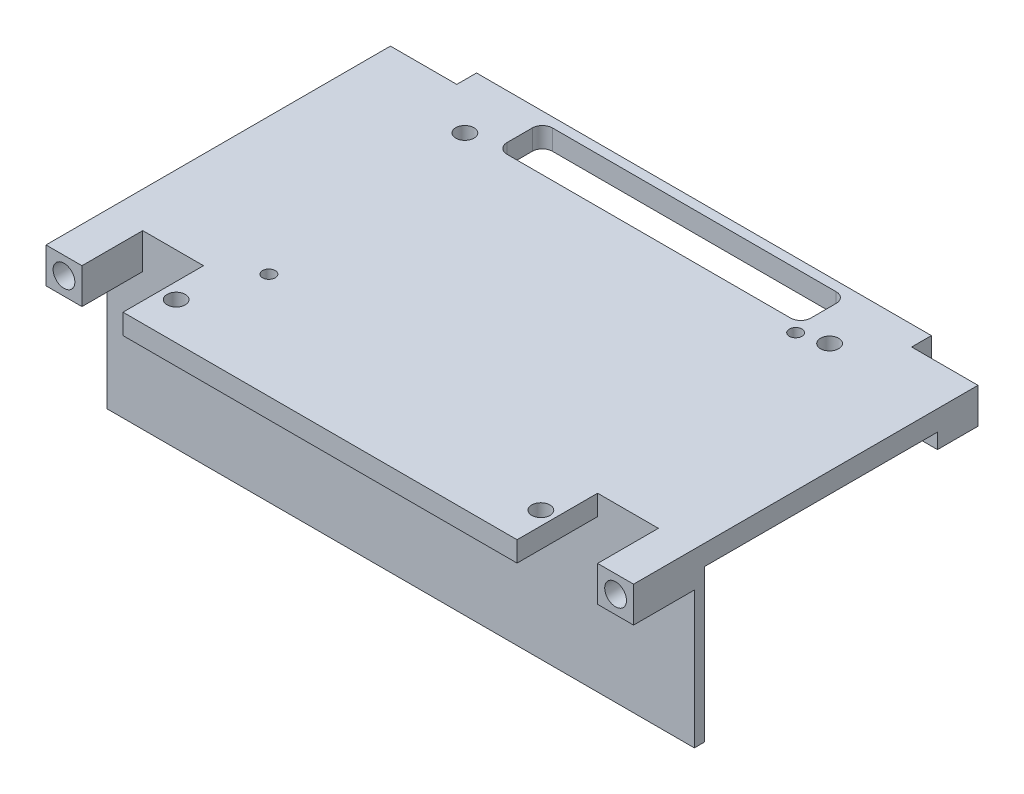
SolidWorks part; units mm, degrees
ref_plane "Front Plane" through (0, 0, 0) normal (0, 0, 1) x (1, 0, 0)
ref_plane "Top Plane" through (0, 0, 0) normal (0, 1, 0) x (1, 0, 0)
ref_plane "Right Plane" through (0, 0, 0) normal (1, 0, 0) x (0, 0, -1)
sketch "Sketch1" plane through (0, 0, 0) normal (0, 1, 0) x (1, 0, 0)
  line L0 (-58, 0) -> (58, 0) construction
  line L1 (-58, -34) -> (-50.9, -34)
  line L2 (-58, -34) -> (-58, 34)
  line L3 (-58, 34) -> (-50.9, 34)
  line L4 (58, -34) -> (58, 34)
  line L5 (-58, -34) -> (58, 34) construction
  line L6 (-58, 34) -> (58, -34) construction
  line L8 (-50.9, 34) -> (-50.9, 41)
  line L9 (-50.9, 41) -> (50.9, 41)
  line L10 (50.9, 34) -> (50.9, 41)
  line L11 (50.9, 34) -> (58, 34)
  line L12 (50.9, -34) -> (50.9, -41)
  line L13 (-50.9, -41) -> (50.9, -41)
  line L14 (-50.9, -34) -> (-50.9, -41)
  line L15 (50.9, -34) -> (58, -34)
  point P0 (0, 0)
  point P10 (0, 41)
  dimension "D1" = 116
  dimension "D2" = 68
  dimension "D3" = 7.1
  dimension "D4" = 7
extrude "Boss-Extrude1" add sketch "Sketch1" along normal blind 4
sketch "Sketch3" plane through (0, 0, 0) normal (0, -1, 0) x (1, 0, 0)
  line L0 (-58, -34) -> (-58, 34) construction
  line L1 (-50.9, -34) -> (-58, -34)
  line L2 (-50.9, -34) -> (-50.9, -26)
  line L3 (-50.9, -26) -> (-58, -26)
  line L4 (-58, -34) -> (-58, -26)
  dimension "D1" = 8
extrude "Boss-Extrude3" add sketch "Sketch3" along normal blind 3
sketch "Sketch4" plane through (0, 0, -34) normal (0, 0, -1) x (-1, 0, 0)
  line L0 (58, -3) -> (50.9, 4) construction
  circle A0 centre (54.45, 0.5) radius 2.15
  dimension "D1" = 4.3
extrude "Cut-Extrude1" cut sketch "Sketch4" against normal blind 7
mirror "Mirror1" about plane through (0, 0, 0) normal (1, 0, 0) of "Cut-Extrude1", "Boss-Extrude3"
mirror "Mirror2" about plane through (0, 0, 0) normal (0, 0, 1) of "Cut-Extrude1", "Boss-Extrude3", "Mirror1"
sketch "Sketch5" plane through (0, 4, 0) normal (0, 1, 0) x (1, 0, 0)
  line L0 (50.9, 41) -> (-50.9, 41) construction
  line L1 (-30, 36) -> (30, 36)
  line L2 (-30, 36) -> (-30, 27)
  line L3 (-30, 27) -> (30, 27)
  line L4 (30, 36) -> (30, 27)
  point P4 (0, 27)
  dimension "D1" = 5
  dimension "D2" = 9
  dimension "D3" = 60
extrude "Cut-Extrude2" cut sketch "Sketch5" against normal through all
sketch "Sketch6" plane through (0, 4, 0) normal (0, 1, 0) x (1, 0, 0)
  line L1 (-38.5, -28) -> (38.5, -28) construction
  line L2 (-38.5, -28) -> (-38.5, 24) construction
  line L3 (-38.5, 24) -> (38.5, 24) construction
  line L4 (38.5, -28) -> (38.5, 24) construction
  line L5 (-38.5, -28) -> (38.5, 24) construction
  line L6 (-38.5, 24) -> (38.5, -28) construction
  circle A0 centre (-38.5, 24) radius 1.25
  circle A1 centre (38.5, 24) radius 1.25
  circle A2 centre (38.5, -28) radius 1.25
  circle A3 centre (-38.5, -28) radius 1.25
  point P0 (0, -2)
  point P9 (0, -2)
  dimension "D4" = 2.5
  dimension "D1" = 77
  dimension "D2" = 52
  dimension "D3" = 2
fillet "Fillet1" radius 2 4 edges at (-30, 2, -36) (-30, 2, -27) (30, 2, -36) (30, 2, -27)
sketch "Sketch7" plane through (0, 4, 0) normal (0, 1, 0) x (1, 0, 0)
  line L0 (50.9, 34) -> (50.9, 41) construction
  line L1 (-50.9, 41) -> (50.9, 41)
  line L2 (-50.9, 41) -> (-50.9, 40)
  line L3 (-50.9, 40) -> (50.9, 40)
  line L4 (50.9, 41) -> (50.9, 40)
  line L5 (-50.9, -34) -> (-50.9, -41) construction
  line L6 (50.9, -41) -> (-50.9, -41)
  line L7 (50.9, -41) -> (50.9, -40)
  line L8 (50.9, -40) -> (-50.9, -40)
  line L9 (-50.9, -41) -> (-50.9, -40)
  dimension "D1" = 1
  dimension "D2" = 1
extrude "Cut-Extrude3" cut sketch "Sketch7" against normal through all
sketch "Sketch8" plane through (0, 0, 0) normal (0, -1, 0) x (1, 0, 0)
  line L0 (58, 26) -> (58, -26) construction
  line L1 (58, 22) -> (-58, 22)
  line L2 (58, 22) -> (58, 20)
  line L3 (58, 20) -> (-58, 20)
  line L4 (-58, 22) -> (-58, 20)
  line L5 (-58, -26) -> (-58, 26) construction
  line L7 (50.9, 40) -> (-50.9, 40) construction
  dimension "D1" = 20
  dimension "D2" = 2
extrude "Boss-Extrude4" add sketch "Sketch8" along normal blind 30
sketch "Sketch9" plane through (0, 4, 0) normal (0, 1, 0) x (1, 0, 0)
  line L0 (58, -22) -> (-58, -22) construction
  line L1 (-50.9, -40) -> (-38.9, -40)
  line L2 (-50.9, -40) -> (-50.9, -22)
  line L3 (-50.9, -22) -> (-38.9, -22)
  line L4 (-38.9, -40) -> (-38.9, -22)
  dimension "D1" = 12
extrude "Cut-Extrude4" cut sketch "Sketch9" against normal blind 10
sketch "Sketch10" plane through (0, -3, 0) normal (0, -1, 0) x (1, 0, 0)
  line L1 (-58, 26) -> (-50.9, 26)
  line L2 (-58, 26) -> (-58, 22)
  line L3 (-58, 22) -> (-50.9, 22)
  line L4 (-50.9, 26) -> (-50.9, 22)
  line L5 (50.9, 26) -> (58, 26)
  line L6 (50.9, 26) -> (50.9, 22)
  line L7 (50.9, 22) -> (58, 22)
  line L8 (58, 26) -> (58, 22)
extrude "Boss-Extrude5" add sketch "Sketch10" against normal up to surface (3 mm away) up to face at (27.2714, 0, 30)
ref_plane "Plane2" through (-51, 0, 0) normal (-1, 0, 0) x (0, 0, 1)
sketch "Sketch12" plane through (-51, 0, 0) normal (-1, 0, 0) x (0, 0, 1)
  line L0 (22, -5.8) -> (22, -16.2)
  line L1 (22, -30) -> (22, -3) construction
  line L2 (22, -16.2) -> (24.7, -13.5)
  line L3 (24.7, -13.5) -> (24.7, -8.5)
  line L4 (24.7, -8.5) -> (22, -5.8)
  line L5 (24.7, -11) -> (22, -11) construction
  line L6 (22, -3) -> (34, -3) construction
  line L7 (24.1, -9) -> (22.6, -9)
  line L8 (24.1, -9) -> (24.1, -13)
  line L9 (24.1, -13) -> (22.6, -13)
  line L10 (22.6, -9) -> (22.6, -13)
  line L11 (22, -20.8) -> (22, -31.2)
  line L12 (22, -31.2) -> (24.7, -28.5)
  line L13 (24.7, -28.5) -> (24.7, -23.5)
  line L14 (24.7, -23.5) -> (22, -20.8)
  line L15 (24.1, -24) -> (22.6, -24)
  line L16 (24.1, -24) -> (24.1, -28)
  line L17 (24.1, -28) -> (22.6, -28)
  line L18 (22.6, -24) -> (22.6, -28)
  line L19 (24.7, -26) -> (22, -26) construction
  point P13 (23.35, -11)
  point P14 (24.1, -11)
  dimension "D1" = 1.5
  dimension "D2" = 0.6
  dimension "D3" = 0.6
  dimension "D4" = 4
  dimension "D5" = 45
  dimension "D6" = 5
  dimension "D7" = 8
  dimension "D8" = 2
extrude "Boss-Extrude6" add sketch "Sketch12" against normal blind 2
ref_plane "Plane3" through (-44.9, 0, 0) normal (1, 0, 0) x (0, 0, -1)
mirror "Mirror3" about plane through (-44.9, 0, 0) normal (1, 0, 0) of "Boss-Extrude6"
sketch "Sketch13" plane through (0, 0, 0) normal (0, -1, 0) x (1, 0, 0)
  line L0 (-28, -27) -> (28, -27) construction
  line L1 (-18, -17.5) -> (18, -17.5)
  line L2 (-18, -17.5) -> (-18, -19.5)
  line L3 (-18, -19.5) -> (18, -19.5)
  line L4 (18, -17.5) -> (18, -19.5)
  point P4 (0, -19.5)
  dimension "D1" = 36
  dimension "D2" = 2
  dimension "D3" = 7.5
extrude "Boss-Extrude7" add sketch "Sketch13" along normal up to surface (30 mm away) up to face at (-22.45, -30, 21.5)
sketch "Sketch14" plane through (0, 0, 0) normal (1, 0, 0) x (0, 0, -1)
  line L3 (-0.25, -38) -> (-0.25, 0) construction
  line L4 (-20, 0) -> (26, 0) construction
  line L13 (-24.1, -13) -> (-24.1, -9) construction
  line L14 (-24.1, -9) -> (-22.6, -9) construction
  line L15 (-22.6, -9) -> (-22.6, -13) construction
  line L16 (-22.6, -13) -> (-24.1, -13) construction
  line L17 (-22, -5.8) -> (-22, -16.2) construction
  line L18 (-22, -16.2) -> (-24.7, -13.5) construction
  line L19 (-24.7, -13.5) -> (-24.7, -8.5) construction
  line L20 (-24.7, -8.5) -> (-22, -5.8) construction
  line L29 (-24.1, -13) -> (-24.1, -9) construction
  line L30 (-24.1, -9) -> (-22.6, -9) construction
  line L31 (-22.6, -9) -> (-22.6, -13) construction
  line L32 (-22.6, -13) -> (-24.1, -13) construction
  line L33 (-22, -5.8) -> (-22, -16.2) construction
  line L34 (-22, -16.2) -> (-24.7, -13.5) construction
  line L35 (-24.7, -13.5) -> (-24.7, -8.5) construction
  line L36 (-24.7, -8.5) -> (-22, -5.8) construction
  line L37 (24.2, -8.5) -> (21.5, -5.8)
  line L38 (24.2, -13.5) -> (24.2, -8.5)
  line L39 (21.5, -16.2) -> (24.2, -13.5)
  line L40 (21.5, -5.8) -> (21.5, -16.2)
  line L41 (22.1, -13) -> (23.6, -13)
  line L42 (22.1, -9) -> (22.1, -13)
  line L43 (23.6, -9) -> (22.1, -9)
  line L44 (23.6, -13) -> (23.6, -9)
extrude "Boss-Extrude8" add sketch "Sketch14" along normal mid plane 2
sketch "Sketch15" plane through (0, 0, 0) normal (1, 0, 0) x (0, 0, -1)
  line L0 (17.5, 0) -> (17.5, -5)
  line L1 (17.5, -30) -> (17.5, 0) construction
  line L2 (17.5, -5) -> (14.6132, 0)
  line L3 (-20, 0) -> (26, 0) construction
  line L4 (14.6132, 0) -> (17.5, 0)
  dimension "D1" = 60
  dimension "D2" = 5
extrude "Boss-Extrude9" add sketch "Sketch15" against normal up to surface and the other way up to surface up to face at (-18, -15, -18.5) other way up to face at (18, -15, -18.5)
sketch "Sketch16" plane through (0, 0, 40) normal (0, 0, 1) x (1, 0, 0)
  line L0 (38, 0) -> (18, -28) construction
  line L1 (38, 0) -> (18, 0)
  line L2 (38, 0) -> (38, -28)
  line L3 (38, -28) -> (18, -28)
  line L4 (18, 0) -> (18, -28)
  line L5 (50.9, 0) -> (-38.9, 0) construction
  line L6 (20.7, -15.8) -> (35.3, -15.8)
  line L7 (20.7, -15.8) -> (20.7, -25)
  line L8 (20.7, -25) -> (35.3, -25)
  line L9 (35.3, -15.8) -> (35.3, -25)
  line L10 (20.7, -15.8) -> (35.3, -25) construction
  line L11 (20.7, -25) -> (35.3, -15.8) construction
  line L12 (58, -30) -> (58, -3) construction
  point P5 (28, -14)
  point P10 (28, -20.4)
  dimension "D1" = 20
  dimension "D2" = 28
  dimension "D3" = 14.6
  dimension "D4" = 9.2
  dimension "D5" = 20
  dimension "D6" = 3
extrude "Boss-Extrude10" add sketch "Sketch16" against normal blind 2.6
sketch "Sketch17" plane through (0, 0, 0) normal (0, -1, 0) x (1, 0, 0)
  line L6 (-38.9, 22) -> (-50.9, 22) construction
  line L7 (50.9, 40) -> (38.9, 40)
  line L8 (50.9, 40) -> (50.9, 22)
  line L9 (50.9, 22) -> (38.9, 22)
  line L10 (38.9, 40) -> (38.9, 22)
  line L13 (-38.9, 40) -> (-38.9, 22) construction
extrude "Cut-Extrude5" cut sketch "Sketch17" against normal through all
sketch "Sketch18" plane through (0, 4, 0) normal (0, 1, 0) x (1, 0, 0)
  line L5 (-50.9, 40) -> (50.9, 40) construction
  line L6 (50.9, 34) -> (44.9, 34)
  line L7 (50.9, 34) -> (50.9, 40)
  line L8 (50.9, 40) -> (44.9, 40)
  line L9 (44.9, 34) -> (44.9, 40)
  line L11 (-50.9, 34) -> (-44.9, 34)
  line L12 (-50.9, 34) -> (-50.9, 40)
  line L13 (-50.9, 40) -> (-44.9, 40)
  line L14 (-44.9, 34) -> (-44.9, 40)
extrude "Cut-Extrude6" cut sketch "Sketch18" against normal through all
sketch "Sketch20" plane through (0, 4, 0) normal (0, 1, 0) x (1, 0, 0)
  line L0 (-31, 25) -> (31, -17) construction
  line L1 (-31, 25) -> (31, 25) construction
  line L2 (-31, 25) -> (-31, -17) construction
  line L3 (-31, -17) -> (31, -17) construction
  line L4 (31, 25) -> (31, -17) construction
  line L5 (-38.5, 26) -> (38.5, 26) construction
  line L6 (-38.5, 26) -> (-38.5, -26) construction
  line L7 (-38.5, -26) -> (38.5, -26) construction
  line L8 (38.5, 26) -> (38.5, -26) construction
  line L11 (38.5, 26) -> (-38.5, -26) construction
  circle A0 centre (-31, 25) radius 3 construction
  circle A1 centre (-31, -17) radius 3 construction
  circle A2 centre (31, -17) radius 3 construction
  circle A3 centre (31, 25) radius 3 construction
  circle A4 centre (-38.5, 26) radius 3 construction
  circle A5 centre (38.5, 26) radius 3 construction
  circle A6 centre (38.5, -26) radius 3 construction
  circle A7 centre (-38.5, -26) radius 3 construction
  point P18 (0, 4)
  dimension "D3" = 6
  dimension "D1" = 42
  dimension "D2" = 62
  dimension "D4" = 4
  dimension "D6" = 77
  dimension "D7" = 52
sketch "Sketch22" plane through (0, 4, 0) normal (0, 1, 0) x (1, 0, 0)
  circle A0 centre (-31, 25) radius 1.25 construction
  circle A1 centre (31, 25) radius 1.25
  circle A2 centre (31, -17) radius 1.25 construction
  circle A3 centre (-31, -17) radius 1.25
  dimension "D1" = 2.5
extrude "Cut-Extrude7" cut sketch "Sketch22" against normal up to surface (4 mm away) up to face at (14, 0, 34.85)
sketch "Sketch25" plane through (0, 0, -19.5) normal (0, 0, -1) x (-1, 0, 0)
  line L0 (58, -30) -> (-58, -30) construction
  line L1 (-18, -30) -> (-12, -30)
  line L2 (-18, -30) -> (-18, 0)
  line L3 (-18, 0) -> (-12, 0)
  line L4 (-12, -30) -> (-12, 0)
  line L5 (-18, -30) -> (-18, 0) construction
  line L6 (18, 0) -> (-18, 0) construction
  line L7 (-18, -30) -> (18, -30) construction
  line L8 (18, 0) -> (12, 0)
  line L9 (18, 0) -> (18, -30)
  line L10 (18, -30) -> (12, -30)
  line L11 (12, 0) -> (12, -30)
  dimension "D1" = 6
extrude "Cut-Extrude11" cut sketch "Sketch25" against normal blind 10
sketch "Sketch26" plane through (-1, 0, 0) normal (-1, 0, 0) x (0, 0, 1)
  line L1 (-20.3582, -5.0992) -> (-27.2016, -5.0992)
  line L2 (-20.3582, -5.0992) -> (-20.3582, -36.3625)
  line L3 (-20.3582, -36.3625) -> (-27.2016, -36.3625)
  line L4 (-27.2016, -5.0992) -> (-27.2016, -36.3625)
  line L5 (22, -5.8) -> (28.5342, -5.8)
  line L6 (22, -5.8) -> (22, -34.3243)
  line L7 (22, -34.3243) -> (28.5342, -34.3243)
  line L8 (28.5342, -5.8) -> (28.5342, -34.3243)
extrude "Cut-Extrude12" cut sketch "Sketch26" against normal through all both and the other way through all
sketch "Sketch27" plane through (0, 4, 0) normal (0, 1, 0) x (1, 0, 0)
  line L1 (-35.8, -30.5) -> (36.2, -30.5) construction
  line L2 (-35.8, -30.5) -> (-35.8, 26.5) construction
  line L3 (-35.8, 26.5) -> (36.2, 26.5) construction
  line L4 (36.2, -30.5) -> (36.2, 26.5) construction
  line L5 (-35.8, -30.5) -> (36.2, 26.5) construction
  line L6 (-35.8, 26.5) -> (36.2, -30.5) construction
  circle A0 centre (-35.8, 26.5) radius 1.25
  circle A1 centre (-35.8, -30.5) radius 1.25
  circle A2 centre (36.2, -30.5) radius 1.25
  circle A3 centre (36.2, 26.5) radius 1.25
  circle A5 centre (31, 25) radius 1.25 construction
  circle A6 centre (31, 25) radius 1.25 construction
  point P0 (0.2, -2)
  dimension "D1" = 72
  dimension "D2" = 57
  dimension "D3" = 2
  dimension "D4" = 0.2
extrude "Cut-Extrude13" cut sketch "Sketch27" against normal through all
sketch "Sketch28" plane through (0, 4, 0) normal (0, 1, 0) x (1, 0, 0)
  line L0 (44.9, 40) -> (44.9, 34) construction
  line L1 (-44.9, 40) -> (44.9, 40)
  line L2 (-44.9, 40) -> (-44.9, 39.4)
  line L3 (-44.9, 39.4) -> (44.9, 39.4)
  line L4 (44.9, 40) -> (44.9, 39.4)
  line L5 (-38.9, -40) -> (-38.9, -22) construction
  line L6 (38.9, -40) -> (-38.9, -40)
  line L7 (38.9, -40) -> (38.9, -39.4)
  line L8 (38.9, -39.4) -> (-38.9, -39.4)
  line L9 (-38.9, -40) -> (-38.9, -39.4)
  dimension "D1" = 0.6
  dimension "D2" = 0.6
extrude "Cut-Extrude14" cut sketch "Sketch28" against normal through all
chamfer "Chamfer1" distance 2 angle 45 1 edges at (28, 0, 37.4)
sketch "Sketch29" plane through (0, 0, 39.4) normal (0, 0, 1) x (1, 0, 0)
  line L1 (18, -28) -> (38, -28)
  line L2 (18, -28) -> (18, 0)
  line L3 (18, 0) -> (38, 0)
  line L4 (38, -28) -> (38, 0)
extrude "Cut-Extrude15" cut sketch "Sketch29" against normal up to surface (17.4 mm away) up to face at (0, -4.6667, 22)
sketch "Sketch30" plane through (0, 4, 0) normal (0, 1, 0) x (1, 0, 0)
  line L0 (44.9, 39.4) -> (44.9, 34) construction
  line L1 (-44.9, 39.4) -> (44.9, 39.4)
  line L2 (-44.9, 39.4) -> (-44.9, 37.9)
  line L3 (-44.9, 37.9) -> (44.9, 37.9)
  line L4 (44.9, 39.4) -> (44.9, 37.9)
  line L5 (-38.9, -39.4) -> (-38.9, -22) construction
  line L6 (38.9, -39.4) -> (-38.9, -39.4)
  line L7 (38.9, -39.4) -> (38.9, -37.9)
  line L8 (38.9, -37.9) -> (-38.9, -37.9)
  line L9 (-38.9, -39.4) -> (-38.9, -37.9)
  dimension "D1" = 1.5
  dimension "D2" = 1.5
sketch "Sketch31" plane through (-1, 0, 0) normal (-1, 0, 0) x (0, 0, 1)
  line L4 (-24.2, -8.5) -> (-24.2, -13.5)
  line L5 (-24.2, -13.5) -> (-21.5, -16.2)
  line L6 (-21.5, -16.2) -> (-21.5, -5.8)
  line L7 (-21.5, -5.8) -> (-24.2, -8.5)
  line L8 (-24.2, -8.5) -> (-24.2, -13.5)
  line L9 (-24.2, -13.5) -> (-21.5, -16.2)
  line L10 (-21.5, -16.2) -> (-21.5, -5.8)
  line L11 (-21.5, -5.8) -> (-24.2, -8.5)
  dimension "D1" = 0
extrude "Cut-Extrude16" cut sketch "Sketch31" against normal up to surface (2 mm away) up to face at (1, -11, -22.85)
extrude "Cut-Extrude17" cut sketch "Sketch30" against normal through all
sketch "Sketch32" plane through (0, 0, -19.5) normal (0, 0, -1) x (-1, 0, 0)
  line L0 (44.9, 0) -> (-44.9, 0) construction
  line L1 (-3, -14) -> (3, -14)
  line L2 (-3, -14) -> (-3, -28)
  line L3 (-3, -28) -> (3, -28)
  line L4 (3, -14) -> (3, -28)
  point P4 (0, -14)
  dimension "D1" = 6
  dimension "D2" = 14
  dimension "D3" = 14
extrude "Boss-Extrude11" add sketch "Sketch32" along normal blind 1
chamfer "Chamfer2" distance 1 angle 45 1 edges at (0, -14, -19.5)
sketch "Sketch33" plane through (0, 0, -20.5) normal (0, 0, -1) x (-1, 0, 0)
  line L0 (-3, -14) -> (3, -28) construction
  line L1 (0, -25) -> (0, -17) construction
  circle A0 centre (0, -17) radius 1.65
  circle A1 centre (0, -25) radius 1.65
  point P7 (0, -21)
  dimension "D2" = 3.3
  dimension "D1" = 8
sketch "Sketch34" plane through (0, 0, -17.5) normal (0, 0, 1) x (1, 0, 0)
  line L4 (3, -28) -> (3, -14)
  line L5 (-3, -28) -> (3, -28)
  line L6 (-3, -14) -> (-3, -28)
  line L7 (3, -14) -> (-3, -14)
  line L8 (3, -28) -> (3, -14)
  line L9 (-3, -28) -> (3, -28)
  line L10 (-3, -14) -> (-3, -28)
  line L11 (3, -14) -> (-3, -14)
  dimension "D1" = 0
extrude "Boss-Extrude12" add sketch "Sketch34" along normal blind 3
chamfer "Chamfer3" distance 3 angle 45 1 edges at (0, -14, -17.5)
extrude "Cut-Extrude18" cut sketch "Sketch33" against normal up to surface (6 mm away) up to face at (0, -21, -14.5)
chamfer "Chamfer4" distance 3 angle 45 1 edges at (0, 0, -19.5)
sketch "Sketch35" plane through (0, 4, 0) normal (0, 1, 0) x (1, 0, 0)
  circle A0 centre (-35.8, 26.5) radius 1.8
  circle A1 centre (36.2, 26.5) radius 1.8
  circle A2 centre (36.2, -30.5) radius 1.8
  circle A3 centre (-35.8, -30.5) radius 1.8
  dimension "D1" = 3.6
extrude "Cut-Extrude19" cut sketch "Sketch35" against normal through all
